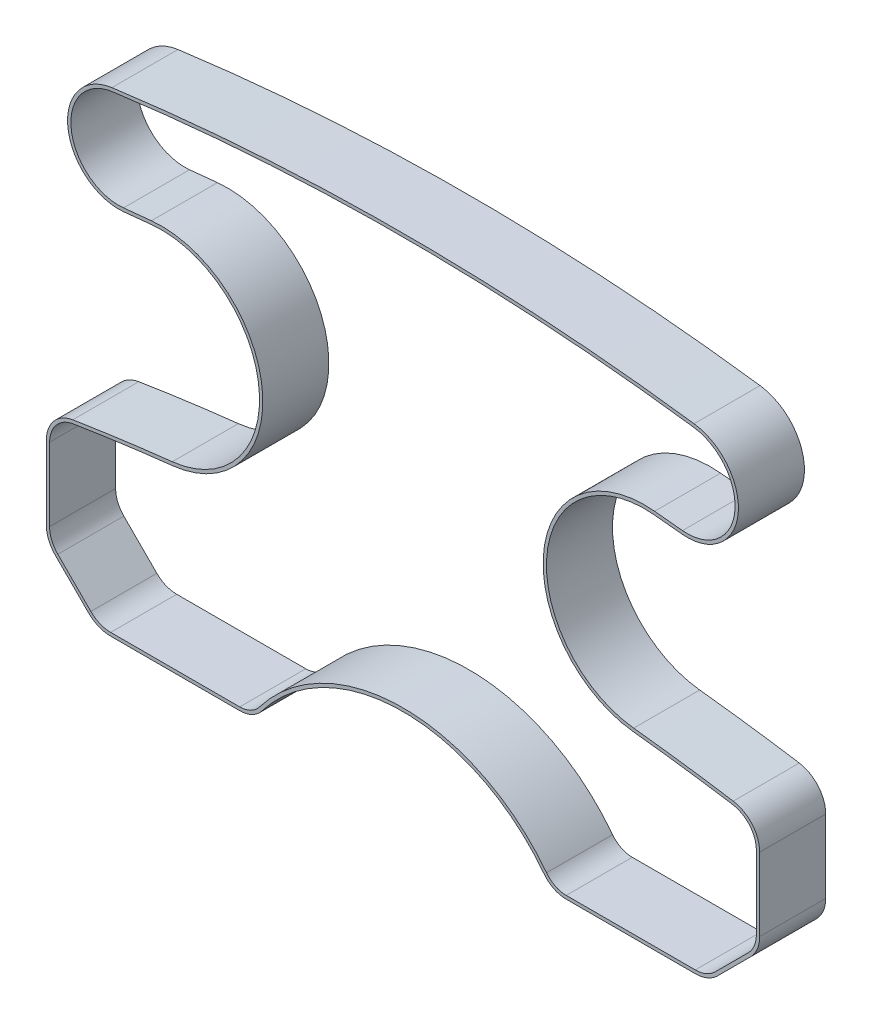
SolidWorks part; units mm, degrees
ref_plane "Front Plane" through (0, 0, 0) normal (0, 0, 1) x (1, 0, 0)
ref_plane "Top Plane" through (0, 0, 0) normal (0, 1, 0) x (1, 0, 0)
ref_plane "Right Plane" through (0, 0, 0) normal (1, 0, 0) x (0, 0, -1)
sketch "Sketch1" plane through (0, 0, 0) normal (0, 0, 1) x (1, 0, 0)
  line L16 (49.4485, -68.5) -> (88.5406, -68.5)
  line L18 (94.551, -66.0104) -> (104.551, -56.0104)
  line L19 (107.0406, -50) -> (107.0406, -27.8625)
  line L34 (76.2055, 45.6457) -> (84.6503, 44.8003)
  line L35 (-84.6503, 44.8003) -> (-76.2055, 45.6457)
  line L36 (-107.0406, -27.8625) -> (-107.0406, -50)
  line L37 (-104.551, -56.0104) -> (-94.551, -66.0104)
  line L38 (-88.5406, -68.5) -> (-49.4485, -68.5)
  line L57 (-88.5406, -69.5) -> (-49.4485, -69.5)
  line L58 (49.4485, -69.5) -> (88.5406, -69.5)
  line L59 (95.2581, -66.7175) -> (105.2581, -56.7175)
  line L60 (108.0406, -50) -> (108.0406, -27.8625)
  line L61 (76.1059, 44.6507) -> (84.5506, 43.8053)
  line L62 (-84.5506, 43.8053) -> (-76.1059, 44.6507)
  line L63 (-108.0406, -27.8625) -> (-108.0406, -50)
  line L64 (-105.2581, -56.7175) -> (-95.2581, -66.7175)
  line L65 (-88.5406, -69.5) -> (-49.4485, -69.5)
  line L66 (49.4485, -69.5) -> (88.5406, -69.5)
  line L67 (95.2581, -66.7175) -> (105.2581, -56.7175)
  line L68 (108.0406, -50) -> (108.0406, -27.8625)
  line L69 (76.1059, 44.6507) -> (84.5506, 43.8053)
  line L70 (-84.5506, 43.8053) -> (-76.1059, 44.6507)
  line L71 (-108.0406, -27.8625) -> (-108.0406, -50)
  line L72 (-105.2581, -56.7175) -> (-95.2581, -66.7175)
  arc A73 (88.5406, -68.5) -> (94.551, -66.0104) centre (88.5406, -60) ccw
  arc A74 (104.551, -56.0104) -> (107.0406, -50) centre (98.5406, -50) ccw
  arc A75 (107.0406, -27.8625) -> (99.8808, -19.4689) centre (98.5406, -27.8625) ccw
  arc A76 (99.8808, -19.4689) -> (69.7683, -15.399) centre (0, -645.0455) ccw
  arc A77 (76.2055, 45.6457) -> (69.7683, -15.399) centre (73.1485, 15.1063) ccw
  arc A78 (84.6503, 44.8003) -> (88.03, 73.5985) centre (86.0945, 59.2282) ccw
  arc A79 (88.03, 73.5985) -> (-88.03, 73.5985) centre (0, -580) ccw
  arc A80 (-88.03, 73.5985) -> (-84.6503, 44.8003) centre (-86.0945, 59.2282) ccw
  arc A81 (-69.7683, -15.399) -> (-76.2055, 45.6457) centre (-73.1485, 15.1063) ccw
  arc A82 (-69.7683, -15.399) -> (-99.8808, -19.4689) centre (0, -645.0455) ccw
  arc A83 (-99.8808, -19.4689) -> (-107.0406, -27.8625) centre (-98.5406, -27.8625) ccw
  arc A84 (-107.0406, -50) -> (-104.551, -56.0104) centre (-98.5406, -50) ccw
  arc A85 (-94.551, -66.0104) -> (-88.5406, -68.5) centre (-88.5406, -60) ccw
  arc A86 (-49.4485, -68.5) -> (-43.4814, -65.5435) centre (-49.4485, -61) ccw
  arc A87 (43.4814, -65.5435) -> (-43.4814, -65.5435) centre (0, -98.6511) ccw
  arc A88 (43.4814, -65.5435) -> (49.4485, -68.5) centre (49.4485, -61) ccw
  arc A89 (-49.4485, -69.5) -> (-42.6858, -66.1493) centre (-49.4485, -61) ccw
  arc A90 (42.6858, -66.1493) -> (-42.6858, -66.1493) centre (0, -98.6511) ccw
  arc A147 (42.6858, -66.1493) -> (49.4485, -69.5) centre (49.4485, -61) ccw
  arc A148 (88.5406, -69.5) -> (95.2581, -66.7175) centre (88.5406, -60) ccw
  arc A149 (105.2581, -56.7175) -> (108.0406, -50) centre (98.5406, -50) ccw
  arc A150 (108.0406, -27.8625) -> (100.0384, -18.4814) centre (98.5406, -27.8625) ccw
  arc A151 (100.0384, -18.4814) -> (69.8784, -14.4051) centre (0, -645.0455) ccw
  arc A152 (76.1059, 44.6507) -> (69.8784, -14.4051) centre (73.1485, 15.1063) ccw
  arc A153 (84.5506, 43.8053) -> (88.1635, 74.5895) centre (86.0945, 59.2282) ccw
  arc A154 (88.1635, 74.5895) -> (-88.1635, 74.5895) centre (0, -580) ccw
  arc A155 (-88.1635, 74.5895) -> (-84.5506, 43.8053) centre (-86.0945, 59.2282) ccw
  arc A156 (-69.8784, -14.4051) -> (-76.1059, 44.6507) centre (-73.1485, 15.1063) ccw
  arc A157 (-69.8784, -14.4051) -> (-100.0384, -18.4814) centre (0, -645.0455) ccw
  arc A158 (-100.0384, -18.4814) -> (-108.0406, -27.8625) centre (-98.5406, -27.8625) ccw
  arc A159 (-108.0406, -50) -> (-105.2581, -56.7175) centre (-98.5406, -50) ccw
  arc A160 (-95.2581, -66.7175) -> (-88.5406, -69.5) centre (-88.5406, -60) ccw
  arc A161 (-49.4485, -69.5) -> (-42.6858, -66.1493) centre (-49.4485, -61) ccw
  arc A162 (42.6858, -66.1493) -> (-42.6858, -66.1493) centre (0, -98.6511) ccw
  arc A163 (42.6858, -66.1493) -> (49.4485, -69.5) centre (49.4485, -61) ccw
  arc A164 (88.5406, -69.5) -> (95.2581, -66.7175) centre (88.5406, -60) ccw
  arc A165 (105.2581, -56.7175) -> (108.0406, -50) centre (98.5406, -50) ccw
  arc A166 (108.0406, -27.8625) -> (100.0384, -18.4814) centre (98.5406, -27.8625) ccw
  arc A167 (100.0384, -18.4814) -> (69.8784, -14.4051) centre (0, -645.0455) ccw
  arc A168 (76.1059, 44.6507) -> (69.8784, -14.4051) centre (73.1485, 15.1063) ccw
  arc A169 (84.5506, 43.8053) -> (88.1635, 74.5895) centre (86.0945, 59.2282) ccw
  arc A170 (88.1635, 74.5895) -> (-88.1635, 74.5895) centre (0, -580) ccw
  arc A171 (-88.1635, 74.5895) -> (-84.5506, 43.8053) centre (-86.0945, 59.2282) ccw
  arc A172 (-69.8784, -14.4051) -> (-76.1059, 44.6507) centre (-73.1485, 15.1063) ccw
  arc A173 (-69.8784, -14.4051) -> (-100.0384, -18.4814) centre (0, -645.0455) ccw
  arc A174 (-100.0384, -18.4814) -> (-108.0406, -27.8625) centre (-98.5406, -27.8625) ccw
  arc A175 (-108.0406, -50) -> (-105.2581, -56.7175) centre (-98.5406, -50) ccw
  arc A176 (-95.2581, -66.7175) -> (-88.5406, -69.5) centre (-88.5406, -60) ccw
  circle A177 centre (88.5406, -60) radius 3.5 construction
  circle A178 centre (98.5406, -50) radius 3.5 construction
  circle A179 centre (78.5406, -50) radius 3.5 construction
  circle A180 centre (88.5406, -40) radius 3.5 construction
  circle A181 centre (98.5406, -27.8625) radius 3.5 construction
  circle A182 centre (78.5406, -25) radius 3.5 construction
  circle A183 centre (88.5406, -60) radius 3.5
  circle A184 centre (98.5406, -50) radius 3.5
  circle A185 centre (78.5406, -50) radius 3.5
  circle A186 centre (88.5406, -40) radius 3.5
  circle A187 centre (98.5406, -27.8625) radius 3.5
  circle A188 centre (78.5406, -25) radius 3.5
  circle A189 centre (42.3209, 63.6101) radius 3.5 construction
  circle A190 centre (61.2596, 62.0843) radius 8 construction
  circle A191 centre (86.0945, 59.2282) radius 8 construction
  circle A192 centre (42.3209, 63.6101) radius 3.5
  circle A193 centre (61.2596, 62.0843) radius 8
  circle A194 centre (86.0945, 59.2282) radius 8
  circle A195 centre (-86.0945, 59.2282) radius 8 construction
  circle A196 centre (-61.2596, 62.0843) radius 8 construction
  circle A197 centre (-42.3209, 63.6101) radius 3.5 construction
  circle A198 centre (-86.0945, 59.2282) radius 8
  circle A199 centre (-61.2596, 62.0843) radius 8
  circle A200 centre (-42.3209, 63.6101) radius 3.5
  circle A201 centre (-78.5406, -50) radius 3.5 construction
  circle A202 centre (-98.5406, -50) radius 3.5 construction
  circle A203 centre (-78.5406, -50) radius 3.5
  circle A204 centre (-98.5406, -50) radius 3.5
  circle A205 centre (-48.1506, -65.36) radius 1.3 construction
  circle A206 centre (-65.9306, -65.36) radius 1.3 construction
  circle A207 centre (-48.1506, -65.36) radius 1.3
  circle A208 centre (-65.9306, -65.36) radius 1.3
  circle A209 centre (-65.9306, -19.64) radius 1.3 construction
  circle A210 centre (-48.1506, -19.64) radius 1.3 construction
  circle A211 centre (-65.9306, -19.64) radius 1.3
  circle A212 centre (-48.1506, -19.64) radius 1.3
  dimension "D1" = 0
  dimension "D2" = 1
extrude "Boss-Extrude1" add sketch "Sketch1" along normal blind 20 contours A85 region at (-92.0754, -68.5338, 0)
